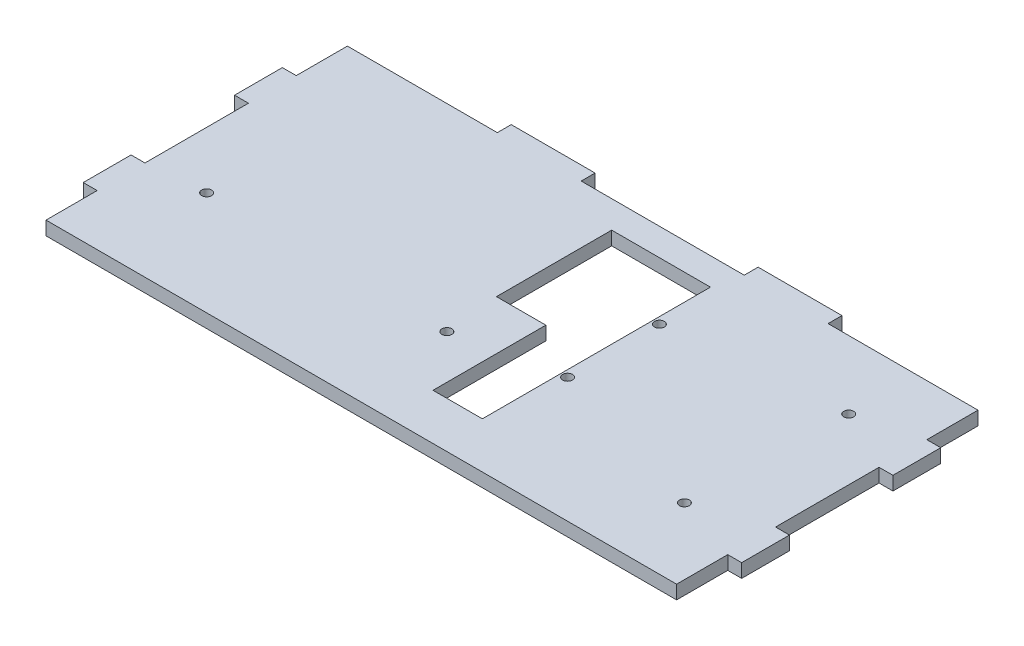
SolidWorks part; units mm, degrees
ref_plane "Front Plane" through (0, 0, 0) normal (0, 0, 1) x (1, 0, 0)
ref_plane "Top Plane" through (0, 0, 0) normal (0, 1, 0) x (1, 0, 0)
ref_plane "Right Plane" through (0, 0, 0) normal (1, 0, 0) x (0, 0, -1)
sketch "Sketch1" plane through (0, 0, 0) normal (0, 1, 0) x (1, 0, 0)
  line L1 (-100, 50) -> (100, 50)
  line L2 (-100, 50) -> (-100, -50)
  line L3 (-100, -50) -> (100, -50)
  line L4 (100, 50) -> (100, -50)
  line L5 (-100, 50) -> (100, -50) construction
  line L6 (-100, -50) -> (100, 50) construction
  point P0 (0, 0)
  dimension "Length" = 200
  dimension "with" = 100
extrude "Boss-Extrude1" add sketch "Sketch1" along normal blind 4.15
sketch "Sketch3" plane through (0, 4.15, 0) normal (0, 1, 0) x (1, 0, 0)
  line L0 (-100, 46.09) -> (-100, 50)
  line L1 (-100, -50) -> (-80.48, -50)
  line L2 (-100, -50) -> (-100, -46.09)
  line L3 (-100, -46.09) -> (-80.48, -46.09)
  line L4 (-80.48, -50) -> (-80.48, -46.09)
  line L5 (-100, 46.09) -> (-80.48, 46.09)
  line L6 (-80.48, 46.09) -> (-80.48, 50)
  line L7 (-100, 50) -> (-80.48, 50)
  line L8 (-60, 46.09) -> (-60, 50)
  line L9 (-60, 46.09) -> (-40.48, 46.09)
  line L10 (-40.48, 46.09) -> (-40.48, 50)
  line L11 (-60, 50) -> (-40.48, 50)
  line L12 (-20, 46.09) -> (-20, 50)
  line L13 (-20, 46.09) -> (-0.48, 46.09)
  line L14 (-0.48, 46.09) -> (-0.48, 50)
  line L15 (-20, 50) -> (-0.48, 50)
  line L16 (20, 46.09) -> (20, 50)
  line L17 (20, 46.09) -> (39.52, 46.09)
  line L18 (39.52, 46.09) -> (39.52, 50)
  line L19 (20, 50) -> (39.52, 50)
  line L20 (60, 46.09) -> (60, 50)
  line L21 (60, 46.09) -> (79.52, 46.09)
  line L22 (79.52, 46.09) -> (79.52, 50)
  line L23 (60, 50) -> (79.52, 50)
  line L24 (-60, -50) -> (-60, -46.09)
  line L25 (-60, -50) -> (-40.48, -50)
  line L26 (-40.48, -50) -> (-40.48, -46.09)
  line L27 (-60, -46.09) -> (-40.48, -46.09)
  line L28 (-20, -50) -> (-20, -46.09)
  line L29 (-20, -50) -> (-0.48, -50)
  line L30 (-0.48, -50) -> (-0.48, -46.09)
  line L31 (-20, -46.09) -> (-0.48, -46.09)
  line L32 (20, -50) -> (20, -46.09)
  line L33 (20, -50) -> (39.52, -50)
  line L34 (39.52, -50) -> (39.52, -46.09)
  line L35 (20, -46.09) -> (39.52, -46.09)
  line L36 (60, -50) -> (60, -46.09)
  line L37 (60, -50) -> (79.52, -50)
  line L38 (79.52, -50) -> (79.52, -46.09)
  line L39 (60, -46.09) -> (79.52, -46.09)
  line L40 (-100, -50) -> (100, -50) construction
  line L41 (100, 50) -> (-100, 50) construction
  point P5 (-80.48, -48.045)
  dimension "D1" = 3.91
  dimension "D2" = 19.52
  dimension "D5" = 20.48
  dimension "D3" = 2
  dimension "D4" = 5
extrude "Cut-Extrude2" [suppressed] cut sketch "Sketch3" against normal blind 10
sketch "Sketch4" plane through (0, 4.15, 0) normal (0, 1, 0) x (1, 0, 0)
  line L0 (-100, 9.76) -> (-100, -9.76)
  line L1 (-100, 9.76) -> (-96.09, 9.76)
  line L2 (-100, -9.76) -> (-96.09, -9.76)
  line L3 (-96.09, 9.76) -> (-96.09, -9.76)
  line L4 (-100, 50) -> (-100, -50) construction
  line L5 (0, -2.2825) -> (0, 2.2825) construction
  line L6 (100, -9.76) -> (96.09, -9.76)
  line L7 (96.09, 9.76) -> (96.09, -9.76)
  line L8 (100, 9.76) -> (96.09, 9.76)
  line L9 (100, 9.76) -> (100, -9.76)
  point P6 (-100, 0)
  dimension "D1" = 19.52
  dimension "D2" = 3.91
extrude "Cut-Extrude3" [suppressed] cut sketch "Sketch4" against normal blind 10
sketch "Sketch5" [suppressed] plane through (0, 4.15, 0) normal (0, 1, 0) x (1, 0, 0)
  line L0 (100, -36.09) -> (100, -40)
  line L1 (100, -36.09) -> (80.48, -36.09)
  line L2 (100, -40) -> (80.48, -40)
  line L3 (80.48, -36.09) -> (80.48, -40)
  line L4 (100, -40) -> (100, -9.76) construction
  line L5 (60, -36.09) -> (60, -40)
  line L6 (60, -36.09) -> (40.48, -36.09)
  line L7 (40.48, -36.09) -> (40.48, -40)
  line L8 (60, -40) -> (40.48, -40)
  line L9 (20, -36.09) -> (20, -40)
  line L10 (20, -36.09) -> (0.48, -36.09)
  line L11 (0.48, -36.09) -> (0.48, -40)
  line L12 (20, -40) -> (0.48, -40)
  line L13 (-20, -36.09) -> (-20, -40)
  line L14 (-20, -36.09) -> (-39.52, -36.09)
  line L15 (-39.52, -36.09) -> (-39.52, -40)
  line L16 (-20, -40) -> (-39.52, -40)
  line L17 (-60, -36.09) -> (-60, -40)
  line L18 (-60, -36.09) -> (-79.52, -36.09)
  line L19 (-79.52, -36.09) -> (-79.52, -40)
  line L20 (-60, -40) -> (-79.52, -40)
  line L21 (60, 40) -> (60, 36.09)
  line L22 (60, 40) -> (40.48, 40)
  line L23 (40.48, 40) -> (40.48, 36.09)
  line L24 (60, 36.09) -> (40.48, 36.09)
  line L25 (20, 40) -> (20, 36.09)
  line L26 (20, 40) -> (0.48, 40)
  line L27 (0.48, 40) -> (0.48, 36.09)
  line L28 (20, 36.09) -> (0.48, 36.09)
  line L29 (-20, 40) -> (-20, 36.09)
  line L30 (-20, 40) -> (-39.52, 40)
  line L31 (-39.52, 40) -> (-39.52, 36.09)
  line L32 (-20, 36.09) -> (-39.52, 36.09)
  line L33 (-60, 40) -> (-60, 36.09)
  line L34 (-60, 40) -> (-79.52, 40)
  line L35 (-79.52, 40) -> (-79.52, 36.09)
  line L36 (-60, 36.09) -> (-79.52, 36.09)
  line L37 (100, 40) -> (100, 36.09)
  line L38 (100, 40) -> (80.48, 40)
  line L39 (80.48, 40) -> (80.48, 36.09)
  line L40 (100, 36.09) -> (80.48, 36.09)
  line L41 (100, 40) -> (-100, 40) construction
  point P9 (100, 38.045)
  point P46 (100, -38.045)
  dimension "D1" = 3.91
  dimension "D2" = 19.52
  dimension "D5" = 20.48
  dimension "D3" = 5
  dimension "D4" = 2
extrude "Cut-Extrude4" [suppressed] cut sketch "Sketch5" against normal blind 10
sketch "Sketch6" [suppressed] plane through (0, 4.15, 0) normal (0, 1, 0) x (1, 0, 0)
  line L4 (-2.2825, 0) -> (2.2825, 0) construction
  line L5 (-40, -50) -> (-10.24, -50)
  line L6 (-40, -50) -> (-40, -46.09)
  line L7 (-40, -46.09) -> (-10.24, -46.09)
  line L8 (-10.24, -50) -> (-10.24, -46.09)
  line L9 (40, -50) -> (10.24, -50)
  line L10 (40, -50) -> (40, -46.09)
  line L11 (40, -46.09) -> (10.24, -46.09)
  line L12 (10.24, -50) -> (10.24, -46.09)
  line L13 (-40, 46.09) -> (-10.24, 46.09)
  line L14 (-10.24, 50) -> (-10.24, 46.09)
  line L15 (-40, 50) -> (-10.24, 50)
  line L16 (-40, 50) -> (-40, 46.09)
  line L17 (40, 46.09) -> (10.24, 46.09)
  line L18 (10.24, 50) -> (10.24, 46.09)
  line L19 (40, 50) -> (10.24, 50)
  line L20 (40, 50) -> (40, 46.09)
  line L21 (0, -2.2825) -> (0, 2.2825) construction
  line L22 (40, -46.09) -> (36.09, -46.09)
  line L23 (40, -46.09) -> (40, -10.24)
  line L24 (40, -10.24) -> (36.09, -10.24)
  line L25 (36.09, -46.09) -> (36.09, -10.24)
  line L26 (40, 46.09) -> (36.09, 46.09)
  line L27 (40, 46.09) -> (40, 10.24)
  line L28 (40, 10.24) -> (36.09, 10.24)
  line L29 (36.09, 46.09) -> (36.09, 10.24)
  line L30 (-40, 10.24) -> (-36.09, 10.24)
  line L31 (-36.09, 46.09) -> (-36.09, 10.24)
  line L32 (-40, 46.09) -> (-36.09, 46.09)
  line L33 (-40, 46.09) -> (-40, 10.24)
  line L34 (-40, -10.24) -> (-36.09, -10.24)
  line L35 (-36.09, -46.09) -> (-36.09, -10.24)
  line L36 (-40, -46.09) -> (-36.09, -46.09)
  line L37 (-40, -46.09) -> (-40, -10.24)
  dimension "D1" = 20.48
  dimension "D2" = 3.91
  dimension "D4" = 29.76
  dimension "D5" = 3.91
  dimension "D6" = 3.91
  dimension "D7" = 20.48
extrude "Cut-Extrude5" [suppressed] cut sketch "Sketch6" against normal blind 10
sketch "Sketch7" [suppressed] plane through (0, 4.15, 0) normal (0, 1, 0) x (1, 0, 0)
  line L0 (39.52, -46.09) -> (20, -46.09) construction
  line L1 (18.8, 13.91) -> (90, 13.91)
  line L2 (18.8, 13.91) -> (18.8, 37.91)
  line L3 (18.8, 37.91) -> (90, 37.91)
  line L4 (90, 13.91) -> (90, 37.91)
  line L5 (100, -50) -> (100, -9.76) construction
  dimension "D1" = 71.2
  dimension "D2" = 24
  dimension "D3" = 60
  dimension "D4" = 10
extrude "Cut-Extrude6" [suppressed] cut sketch "Sketch7" against normal blind 10
sketch "Sketch8" [suppressed] plane through (0, 4.15, 0) normal (0, 1, 0) x (1, 0, 0)
  line L0 (18.8, 37.91) -> (18.8, 13.91) construction
  line L1 (90, 13.91) -> (90, 37.91) construction
  line L4 (90, 37.91) -> (18.8, 37.91) construction
  line L5 (18.8, 13.91) -> (90, 13.91) construction
  circle A0 centre (16.9, 10.16) radius 1.5
  circle A1 centre (16.9, 41.66) radius 1.5
  circle A2 centre (91.9, 41.66) radius 1.5
  circle A3 centre (91.9, 10.16) radius 1.5
  dimension "D1" = 2
  dimension "D3" = 3
  dimension "D7" = 1.9
  dimension "D4" = 3.75
  dimension "D5" = 3.75
  dimension "D6" = 1.9
  dimension "D2" = 2
extrude "Cut-Extrude7" [suppressed] cut sketch "Sketch8" against normal blind 10
sketch "Sketch9" [suppressed] plane through (0, 4.15, 0) normal (0, 1, 0) x (1, 0, 0)
  line L0 (-0.48, -46.09) -> (-20, -46.09) construction
  line L1 (8.8, 3.91) -> (5.4, 3.91)
  line L2 (8.8, 3.91) -> (8.8, 42.91)
  line L3 (8.8, 42.91) -> (5.4, 42.91)
  line L4 (5.4, 3.91) -> (5.4, 42.91)
  line L5 (18.8, 37.91) -> (18.8, 13.91) construction
  dimension "D1" = 3.4
  dimension "D2" = 39
  dimension "D3" = 50
  dimension "D4" = 10
extrude "Cut-Extrude8" [suppressed] cut sketch "Sketch9" against normal blind 10
sketch "Sketch10" [suppressed] plane through (0, 4.15, 0) normal (0, 1, 0) x (1, 0, 0)
  line L1 (96.09, 9.76) -> (96.09, -9.76) construction
  line L3 (39.52, -46.09) -> (20, -46.09) construction
  circle A0 centre (26.09, 3.91) radius 3.425
  dimension "D1" = 6.85
  dimension "D2" = 50
  dimension "D3" = 70
extrude "Cut-Extrude9" [suppressed] cut sketch "Sketch10" against normal blind 10 contours A0
sketch "Sketch11" [suppressed] plane through (0, 4.15, 0) normal (0, 1, 0) x (1, 0, 0)
  line L1 (96.09, 9.76) -> (96.09, -9.76) construction
  line L4 (39.52, -46.09) -> (20, -46.09) construction
  circle A0 centre (41.09, 3.91) radius 3.125
  circle A1 centre (53.09, 3.91) radius 3.125
  dimension "D1" = 6.25
  dimension "D3" = 55
  dimension "D5" = 12
  dimension "D2" = 50
  dimension "D4" = 2
extrude "Cut-Extrude10" [suppressed] cut sketch "Sketch11" against normal blind 10
sketch "Sketch12" [suppressed] plane through (0, 4.15, 0) normal (0, 1, 0) x (1, 0, 0)
  line L1 (96.09, 9.76) -> (96.09, -9.76) construction
  line L2 (79.52, -46.09) -> (60, -46.09) construction
  circle A0 centre (68.09, 3.91) radius 3.825
  circle A1 centre (81.09, 3.91) radius 3.825
  dimension "D1" = 7.65
  dimension "D2" = 50
  dimension "D4" = 28
  dimension "D5" = 15
  dimension "D6" = 50
  dimension "D3" = 2
sketch "Sketch13" plane through (0, 4.15, 0) normal (0, 1, 0) x (1, 0, 0)
  line L0 (100, -50) -> (100, 50) construction
  line L1 (24.76, 50) -> (-24.76, 50)
  line L3 (24.76, 45.78) -> (-24.76, 45.78)
  line L4 (-24.76, 50) -> (-24.76, 45.78)
  line L5 (0, -2.2825) -> (0, 2.2825) construction
  line L6 (-100, 50) -> (-50.24, 50)
  line L8 (-95.78, 45.78) -> (-50.24, 45.78)
  line L9 (-50.24, 50) -> (-50.24, 45.78)
  line L10 (95.78, 45.78) -> (50.24, 45.78)
  line L11 (50.24, 50) -> (50.24, 45.78)
  line L12 (100, 50) -> (50.24, 50)
  line L14 (24.76, 50) -> (24.76, 45.78)
  line L15 (-100, 50) -> (-100, -50) construction
  line L21 (-100, -15.72) -> (-100, 15.72)
  line L22 (-100, 15.72) -> (-95.78, 15.72)
  line L23 (-95.78, -15.72) -> (-95.78, 15.72)
  line L24 (-2.2825, 0) -> (2.2825, 0) construction
  line L26 (-100, 50) -> (-100, 30.24)
  line L27 (-100, 30.24) -> (-95.78, 30.24)
  line L28 (-95.78, 45.78) -> (-95.78, 30.24)
  line L29 (-100, -15.72) -> (-95.78, -15.72)
  line L30 (-100, -30.24) -> (-95.78, -30.24)
  line L31 (-95.78, -50) -> (-95.78, -30.24)
  line L32 (-100, -50) -> (-95.78, -50)
  line L33 (-100, -50) -> (-100, -30.24)
  line L34 (100, 30.24) -> (95.78, 30.24)
  line L35 (95.78, 45.78) -> (95.78, 30.24)
  line L37 (100, 50) -> (100, 30.24)
  line L38 (100, -15.72) -> (100, 15.72)
  line L39 (100, 15.72) -> (95.78, 15.72)
  line L40 (95.78, -15.72) -> (95.78, 15.72)
  line L41 (100, -15.72) -> (95.78, -15.72)
  line L42 (100, -50) -> (100, -30.24)
  line L43 (100, -50) -> (95.78, -50)
  line L44 (95.78, -50) -> (95.78, -30.24)
  line L45 (100, -30.24) -> (95.78, -30.24)
  line L46 (-100, -50) -> (100, -50) construction
  line L47 (100, 50) -> (-100, 50) construction
  dimension "D1" = 4.22
  dimension "D2" = 49.76
  dimension "D3" = 25.48
  dimension "D4" = 4.22
  dimension "D5" = 19.76
  dimension "D6" = 4.22
  dimension "D7" = 4.22
  dimension "D8" = 14.52
  dimension "D9" = 31.44
extrude "Cut-Extrude12" cut sketch "Sketch13" against normal blind 10
sketch "Sketch14" plane through (0, 4.15, 0) normal (0, 1, 0) x (1, 0, 0)
  line L0 (95.78, -30.24) -> (95.78, -50) construction
  line L1 (-96.02, -50) -> (95.78, -50)
  line L2 (-96.02, -50) -> (-96.02, -45.78)
  line L3 (-96.02, -45.78) -> (95.78, -45.78)
  line L4 (95.78, -50) -> (95.78, -45.78)
  dimension "D1" = 4.22
extrude "Cut-Extrude13" cut sketch "Sketch14" against normal blind 10
sketch "Sketch15" [suppressed] plane through (0, 4.15, 0) normal (0, 1, 0) x (1, 0, 0)
  line L0 (10.24, 50) -> (-10.24, 50) construction
  line L1 (2.35, 30) -> (-1.63, 30)
  line L2 (2.35, 30) -> (2.35, 15.48)
  line L3 (2.35, 15.48) -> (-1.63, 15.48)
  line L4 (-1.63, 30) -> (-1.63, 15.48)
  line L5 (2.35, 30) -> (-1.63, 15.48) construction
  line L6 (2.35, 15.48) -> (-1.63, 30) construction
  line L7 (36.09, 46.09) -> (36.09, 10.24) construction
  line L9 (-2.2825, 0) -> (2.2825, 0) construction
  line L10 (2.35, -15.48) -> (-1.63, -15.48)
  line L11 (-1.63, -30) -> (-1.63, -15.48)
  line L12 (2.35, -30) -> (-1.63, -30)
  line L13 (2.35, -30) -> (2.35, -15.48)
  point P0 (0.36, 22.74)
  dimension "D1" = 20
  dimension "D2" = 14.52
  dimension "D3" = 33.74
  dimension "D4" = 3.98
extrude "Cut-Extrude14" [suppressed] cut sketch "Sketch15" against normal blind 10
sketch "Sketch16" [suppressed] plane through (0, 4.15, 0) normal (0, 1, 0) x (1, 0, 0)
  line L1 (-25.24, 2.195) -> (-50.48, 2.195)
  line L2 (-25.24, 2.195) -> (-25.24, -2.195)
  line L3 (-25.24, -2.195) -> (-50.48, -2.195)
  line L4 (-50.48, 2.195) -> (-50.48, -2.195)
  line L5 (-25.24, 2.195) -> (-50.48, -2.195) construction
  line L6 (-25.24, -2.195) -> (-50.48, 2.195) construction
  line L8 (0, -2.2825) -> (0, 2.2825) construction
  line L9 (25.24, -2.195) -> (50.48, -2.195)
  line L10 (50.48, 2.195) -> (50.48, -2.195)
  line L11 (25.24, 2.195) -> (50.48, 2.195)
  line L12 (25.24, 2.195) -> (25.24, -2.195)
  line L13 (-25.24, -36.09) -> (-25.24, 36.09) construction
  line L14 (-20, -36.09) -> (-39.52, -36.09) construction
  line L15 (-39.52, 36.09) -> (-20, 36.09) construction
  line L16 (-100, 40) -> (-100, 9.76) construction
  point P0 (-37.86, 0)
  point P5 (-25.24, 0)
  point P6 (-25.24, 0)
  point P7 (25.24, 0)
  dimension "D1" = 4.39
  dimension "D2" = 49.52
  dimension "D3" = 25.24
extrude "Cut-Extrude15" [suppressed] cut sketch "Sketch16" against normal blind 10
sketch "Sketch18" plane through (0, 4.15, 0) normal (0, 1, 0) x (1, 0, 0)
  line L0 (95.78, 15.72) -> (95.78, -15.72) construction
  line L1 (12.78, 37.5) -> (22.78, 37.5)
  line L3 (7.78, -31.78) -> (22.78, -31.78)
  line L4 (22.78, 37.5) -> (22.78, -31.78)
  line L5 (7.78, 2.5) -> (7.78, -31.78)
  line L6 (12.78, 37.5) -> (-7.22, 37.5)
  line L10 (95.78, -45.78) -> (-95.78, -45.78) construction
  line L11 (-24.76, 45.78) -> (24.76, 45.78) construction
  line L14 (7.78, 2.5) -> (-7.22, 2.5)
  line L15 (-7.22, 37.5) -> (-7.22, 2.5)
  dimension "D1" = 15
  dimension "D2" = 8.28
  dimension "D3" = 73
  dimension "D4" = 14
  dimension "D6" = 35
  dimension "D7" = 15
extrude "Cut-Extrude18" cut sketch "Sketch18" against normal blind 10
sketch "Sketch19" [suppressed] plane through (0, 4.15, 0) normal (0, 1, 0) x (1, 0, 0)
  line L0 (5.4, 42.91) -> (5.4, 3.91) construction
  line L1 (-2.1, 25.91) -> (0.9, 25.91)
  line L2 (-2.1, 25.91) -> (-2.1, 20.91)
  line L3 (-2.1, 20.91) -> (0.9, 20.91)
  line L4 (0.9, 25.91) -> (0.9, 20.91)
  line L5 (-2.1, 25.91) -> (0.9, 20.91) construction
  line L6 (-2.1, 20.91) -> (0.9, 25.91) construction
  point P0 (-0.6, 23.41)
  point P7 (5.4, 23.41)
  point P8 (0.9, 23.41)
  dimension "D1" = 4.5
  dimension "D2" = 3
  dimension "D4" = 5
extrude "Cut-Extrude19" [suppressed] cut sketch "Sketch19" against normal blind 4.2
sketch "Sketch20" plane through (0, 4.15, 0) normal (0, 1, 0) x (1, 0, 0)
  line L0 (100, -30.24) -> (100, -15.72) construction
  line L1 (-1.85, -18.28) -> (1.15, -18.28)
  line L2 (-1.85, -18.28) -> (-1.85, -23.28)
  line L3 (-1.85, -23.28) -> (1.15, -23.28)
  line L4 (1.15, -18.28) -> (1.15, -23.28)
  line L5 (-1.85, -18.28) -> (1.15, -23.28) construction
  line L6 (-1.85, -23.28) -> (1.15, -18.28) construction
  line L8 (95.78, -45.78) -> (-95.78, -45.78) construction
  point P0 (-0.35, -20.78)
  dimension "D1" = 22.5
  dimension "D2" = 98.85
  dimension "D3" = 3
  dimension "D4" = 5
extrude "Cut-Extrude21" [suppressed] cut sketch "Sketch20" against normal blind 4.2
sketch "Sketch21" [suppressed] plane through (0, 4.15, 0) normal (0, 1, 0) x (1, 0, 0)
  line L0 (100, 9.76) -> (100, 50) construction
  line L1 (35.9, 25.91) -> (40.9, 25.91)
  line L2 (35.9, 25.91) -> (35.9, 20.91)
  line L3 (35.9, 20.91) -> (40.9, 20.91)
  line L4 (40.9, 25.91) -> (40.9, 20.91)
  line L5 (35.9, 25.91) -> (40.9, 20.91) construction
  line L6 (35.9, 20.91) -> (40.9, 25.91) construction
  line L7 (-100, 46.09) -> (-80.48, 46.09) construction
  line L9 (-84.59, 25.91) -> (-79.59, 25.91)
  line L10 (-84.59, 25.91) -> (-84.59, 20.91)
  line L11 (-84.59, 20.91) -> (-79.59, 20.91)
  line L12 (-79.59, 25.91) -> (-79.59, 20.91)
  line L13 (20, 46.09) -> (39.52, 46.09) construction
  point P0 (38.4, 23.41)
  dimension "D1" = 5
  dimension "D2" = 5
  dimension "D3" = 59.1
  dimension "D4" = 20.18
  dimension "D5" = 5
  dimension "D6" = 5
  dimension "D7" = 125.49
  dimension "D8" = 20.18
extrude "Cut-Extrude22" [suppressed] cut sketch "Sketch21" against normal blind 4.2
sketch "Sketch22" plane through (0, 4.15, 0) normal (0, 1, 0) x (1, 0, 0)
  line L1 (-24.76, 45.78) -> (24.76, 45.78) construction
  line L2 (-95.78, -15.72) -> (-95.78, 15.72) construction
  circle A0 centre (-78.55, -14.22) radius 1.5
  circle A1 centre (-5.55, -14.22) radius 1.5
  dimension "D1" = 3
  dimension "D2" = 3
  dimension "D3" = 73
  dimension "D4" = 17.23
  dimension "D5" = 60
extrude "Cut-Extrude23" cut sketch "Sketch22" against normal blind 10
extrude "Cut-Extrude24" [suppressed] cut sketch "Sketch12" against normal blind 10
sketch "Sketch23" [suppressed] plane through (0, 4.15, 0) normal (0, 1, 0) x (1, 0, 0)
  line L0 (-96.09, -9.76) -> (-96.09, 9.76) construction
  line L1 (32.91, 30.75) -> (-65.09, 30.75)
  line L2 (32.91, 30.75) -> (32.91, -30.75)
  line L3 (32.91, -30.75) -> (-65.09, -30.75)
  line L4 (-65.09, 30.75) -> (-65.09, -30.75)
  line L7 (-40.48, -46.09) -> (-60, -46.09) construction
  point P6 (-96.09, 0)
  dimension "D1" = 98
  dimension "D2" = 61.5
  dimension "D3" = 31
  dimension "D4" = 15.34
extrude "Cut-Extrude25" [suppressed] cut sketch "Sketch23" against normal blind 10
sketch "Sketch24" [suppressed] plane through (0, 4.15, 0) normal (0, 1, 0) x (1, 0, 0)
  line L0 (-100, -9.76) -> (-100, -46.09) construction
  line L2 (-80.48, -50) -> (-60, -50) construction
  circle A0 centre (-70.79, -21.8) radius 1.5
  dimension "D1" = 3
  dimension "D2" = 29.21
  dimension "D3" = 28.2
extrude "Cut-Extrude26" [suppressed] cut sketch "Sketch24" against normal blind 10
mirror "Mirror1" [suppressed] about plane through (0, 0, 0) normal (0, 0, 1)
sketch "Sketch25" plane through (0, 4.15, 0) normal (0, 1, 0) x (1, 0, 0)
  line L0 (50.24, 50) -> (24.76, 50) construction
  line L1 (22.78, -31.78) -> (22.78, 37.5) construction
  circle A0 centre (24.78, 20) radius 1.5
  circle A1 centre (24.78, -7.9) radius 1.5
  circle A2 centre (77.18, 25.1) radius 1.5
  circle A3 centre (75.58, -23.2) radius 1.5
  dimension "D1" = 3
  dimension "D2" = 27.9
  dimension "D3" = 50.8
  dimension "D4" = 15.3
  dimension "D8" = 2
  dimension "D5" = 52.4
  dimension "D6" = 48.3
  dimension "D7" = 30
extrude "Cut-Extrude27" cut sketch "Sketch25" against normal blind 10
equation "\"kerf\"=0.24"
equation "\"D5@Sketch5\"=20 + 2*\"kerf\""
